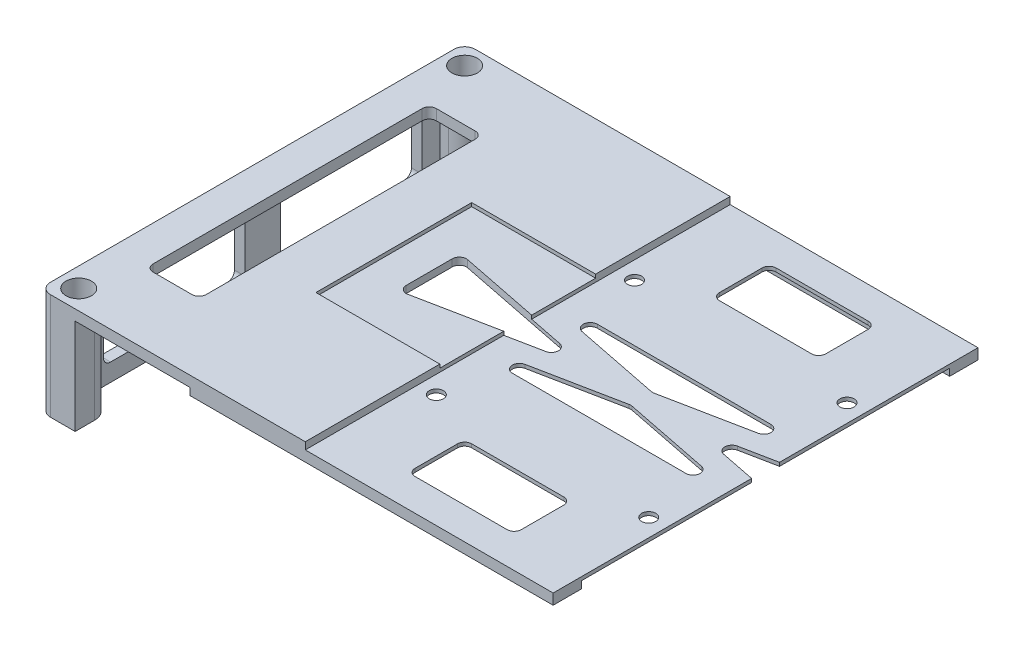
SolidWorks part; units mm, degrees
material "ABS"
ref_plane "前基準面" through (0, 0, 0) normal (0, 0, 1) x (1, 0, 0)
ref_plane "上基準面" through (0, 0, 0) normal (0, 1, 0) x (1, 0, 0)
ref_plane "右基準面" through (0, 0, 0) normal (1, 0, 0) x (0, 0, -1)
sketch "草圖8" plane through (0, 0, 0) normal (0, 1, 0) x (1, 0, 0)
  line L1 (-110, 60) -> (110, 60)
  line L2 (-110, 60) -> (-110, -60)
  line L3 (-110, -60) -> (110, -60)
  line L4 (110, 60) -> (110, -60)
extrude "填料-伸長6" add sketch "草圖8" along normal blind 3
sketch "草圖10" plane through (0, 0, 0) normal (0, -1, 0) x (1, 0, 0)
  line L1 (-110, 60) -> (-100, 60)
  line L2 (-110, 60) -> (-110, -60)
  line L3 (-110, -60) -> (-100, -60)
  line L4 (-100, 60) -> (-100, -60)
  line L5 (0, 0) -> (0, 67.9588) construction
  line L6 (0, 0) -> (59.8785, 0) construction
  line L7 (110, -60) -> (100, -60)
  line L8 (100, 60) -> (100, -60)
  line L9 (110, 60) -> (100, 60)
  line L10 (110, 60) -> (110, -60)
  dimension "D2" = 10
extrude "填料-伸長7" add sketch "草圖10" along normal blind 27
sketch "草圖9" plane through (0, 0, 0) normal (0, 1, 0) x (1, 0, 0)
  line L0 (-1000, 0) -> (49000, 0) construction
  line L1 (0, -994.7968) -> (0, 49005.2032) construction
  line L2 (110, 60) -> (-110, 60) construction
  line L4 (110, -60) -> (110, 60) construction
  circle A0 centre (104.5, 54.5) radius 2.05
  circle A1 centre (-104.5, 54.5) radius 2.05
  circle A2 centre (-104.5, -54.5) radius 2.05
  circle A3 centre (104.5, -54.5) radius 2.05
  circle A6 centre (30, 28) radius 2
  circle A7 centre (-30, 28) radius 2
  circle A8 centre (30, -28) radius 2
  circle A9 centre (-30, -28) radius 2
  dimension "D1" = 4.1
  dimension "D5" = 4
  dimension "D2" = 5.5
  dimension "D3" = 5.5
  dimension "D6" = 30
  dimension "D7" = 28
extrude "除料-伸長1" cut sketch "草圖9" against normal through all and the other way through all contours A1 | A2 | A0 | A3
sketch "草圖11" plane through (0, 3, 0) normal (0, 1, 0) x (1, 0, 0)
  line L0 (0.0013, 21.2615) -> (0.0013, 0) construction
  line L1 (0.0013, 0) -> (-26.9987, 0) construction
  line L2 (110, -60) -> (110, 60) construction
  line L3 (110, 60) -> (-110, 60) construction
  circle A0 centre (-104.4974, 54.5) radius 3.6
  circle A1 centre (-104.4974, -54.5) radius 3.6
  circle A2 centre (104.5, -54.5) radius 3.6
  circle A3 centre (104.5, 54.5) radius 3.6
  dimension "D1" = 7.2
  dimension "D2" = 5.5
  dimension "D4" = 5.5
extrude "除料-伸長2" cut sketch "草圖11" against normal blind 22 contours A1 | A0 | A3 | A2
sketch "草圖13" plane through (0, 0, 0) normal (1, 0, 0) x (0, 0, -1)
  line L0 (0, 0) -> (0, -20.0336) construction
  line L2 (-45, -3.5) -> (-5, -3.5)
  line L3 (-45, -3.5) -> (-45, -22)
  line L4 (-45, -22) -> (-5, -22)
  line L5 (-5, -3.5) -> (-5, -22)
  line L6 (60, -27) -> (-60, -27) construction
  line L8 (45, -3.5) -> (45, -22)
  line L9 (5, -3.5) -> (5, -22)
  line L10 (45, -22) -> (5, -22)
  line L11 (45, -3.5) -> (5, -3.5)
  line L12 (-60, 3) -> (-60, -27) construction
  dimension "D1" = 18.5
  dimension "D2" = 5
  dimension "D3" = 15
  dimension "D4" = 10
extrude "除料-伸長4" cut sketch "草圖13" against normal through all both and the other way through all
sketch "草圖14" plane through (0, 3, 0) normal (0, 1, 0) x (1, 0, 0)
  line L0 (0, 0) -> (-46.215, 0) construction
  line L1 (0, 0) -> (0, 32.6806) construction
  line L3 (-70, -22) -> (70, -22)
  line L4 (-70, -22) -> (-70, 22)
  line L5 (-70, 22) -> (70, 22)
  line L6 (70, -22) -> (70, 22)
  line L7 (-70, -22) -> (70, 22) construction
  line L8 (-70, 22) -> (70, -22) construction
  dimension "D1" = 140
  dimension "D2" = 44
extrude "除料-伸長7" cut sketch "草圖14" against normal blind 1
sketch "草圖15" plane through (0, 3, 0) normal (0, 1, 0) x (1, 0, 0)
  line L0 (0, 0) -> (27.6246, 0) construction
  line L1 (-100, 40) -> (-85, 40)
  line L2 (-100, 40) -> (-100, -40)
  line L3 (-100, -40) -> (-85, -40)
  line L4 (-85, 40) -> (-85, -40)
  line L5 (0, 0) -> (0, 35.214) construction
  line L6 (100, 5) -> (85, 5)
  line L7 (85, 45) -> (85, 5)
  line L8 (100, 45) -> (85, 45)
  line L9 (100, 45) -> (100, 5)
  line L10 (70, 22) -> (-70, 22) construction
  line L11 (-44.7029, -12) -> (44.7029, -12)
  line L12 (-60, -8.9406) -> (-60, 8.9406)
  line L13 (-44.7029, 12) -> (44.7029, 12)
  line L14 (60, -8.9406) -> (60, 8.9406)
  line L15 (-15, -35) -> (15, -35)
  line L16 (0, -3.0594) -> (44.7029, -12)
  line L17 (-70, 22) -> (-70, -22) construction
  line L18 (-60, 8.9406) -> (-15.2971, 0)
  line L19 (-44.7029, -12) -> (0, -3.0594)
  line L20 (-44.7029, 12) -> (0, 3.0594)
  line L21 (-60, -8.9406) -> (-15.2971, 0)
  line L22 (-15, 51) -> (15, 51)
  line L23 (-15, 51) -> (-15, 35)
  line L24 (-15, 35) -> (15, 35)
  line L25 (15, 51) -> (15, 35)
  line L26 (15, -51) -> (15, -35)
  line L27 (-15, -51) -> (15, -51)
  line L28 (15.2971, 0) -> (60, -8.9406)
  line L29 (0, 3.0594) -> (44.7029, 12)
  line L30 (15.2971, 0) -> (60, 8.9406)
  line L31 (-15, -51) -> (-15, -35)
  line L32 (100, -45) -> (100, -5)
  line L33 (100, -45) -> (85, -45)
  line L34 (85, -45) -> (85, -5)
  line L35 (100, -5) -> (85, -5)
  line L36 (110, 60) -> (-110, 60) construction
  dimension "D1" = 40
  dimension "D2" = 85
  dimension "D3" = 15
  dimension "D4" = 10
  dimension "D5" = 10
  dimension "D6" = 30
  dimension "D7" = 16
  dimension "D8" = 35
  dimension "D9" = 85
  dimension "D10" = 80
  dimension "D11" = 15
extrude "除料-伸長8" cut sketch "草圖15" against normal through all
extrude "除料-伸長9" cut sketch "草圖9<5>" along normal through all contours A7 | A6 | A9 | A8
sketch "草圖9<5>" plane through (0, 0, 0) normal (0, 1, 0) x (1, 0, 0) same geometry as "草圖9"
sketch "草圖19" plane through (0, -27, 0) normal (0, -1, 0) x (1, 0, 0)
  line L5 (0, -57.1205) -> (0, 57.1205) construction
  line L6 (0, 0) -> (-76.5655, 0) construction
  line L12 (-100, 54.5) -> (-100, -54.5)
  line L15 (-110, 60) -> (-110, -60) construction
  line L16 (-104.5, 50) -> (-107, 50)
  line L18 (-104.5, -50) -> (-107, -50)
  line L19 (-107, 50) -> (-107, -50)
  line L20 (100, 54.5) -> (100, -54.5)
  line L21 (104.5, -50) -> (107, -50)
  line L22 (107, 50) -> (107, -50)
  line L23 (104.5, 50) -> (107, 50)
  arc A0 (-104.5, 50) -> (-100, 54.5) centre (-104.5, 54.5) ccw
  arc A1 (-104.5, -50) -> (-100, -54.5) centre (-104.5, -54.5) cw
  arc A4 (104.5, 50) -> (100, 54.5) centre (104.5, 54.5) cw
  arc A5 (104.5, -50) -> (100, -54.5) centre (104.5, -54.5) ccw
  point P10 (0, 0)
  dimension "D2" = 9
  dimension "D1" = 3
extrude "除料-伸長13" cut sketch "草圖19" against normal blind 27
sketch "草圖20" plane through (0, 0, 0) normal (0, -1, 0) x (1, 0, 0)
  line L0 (0, 0) -> (0, 103.9697) construction
  line L1 (0, 0) -> (143.2508, 0) construction
  line L2 (-100, 60) -> (100, 60) construction
  line L3 (-67.5, 60) -> (67.5, 60)
  line L4 (-67.5, 60) -> (-67.5, 52)
  line L5 (-67.5, 52) -> (67.5, 52)
  line L6 (67.5, 60) -> (67.5, 52)
  line L7 (-67.5, -52) -> (67.5, -52)
  line L8 (67.5, -60) -> (67.5, -52)
  line L9 (-67.5, -60) -> (67.5, -60)
  line L10 (-67.5, -60) -> (-67.5, -52)
  line L12 (-59, 32.5) -> (-39, 32.5)
  line L13 (-59, 32.5) -> (-59, 25)
  line L14 (-59, 25) -> (-54, 25)
  line L15 (-39, 32.5) -> (-39, 29.5)
  line L28 (-85, 40) -> (-85, -40) construction
  line L31 (-54, 25) -> (-54, 29.5)
  line L32 (-54, 29.5) -> (-39, 29.5)
  line L33 (54, 29.5) -> (39, 29.5)
  line L34 (54, 25) -> (54, 29.5)
  line L35 (39, 32.5) -> (39, 29.5)
  line L36 (59, 25) -> (54, 25)
  line L37 (59, 32.5) -> (59, 25)
  line L38 (59, 32.5) -> (39, 32.5)
  line L39 (59, -32.5) -> (39, -32.5)
  line L40 (59, -32.5) -> (59, -25)
  line L41 (59, -25) -> (54, -25)
  line L42 (39, -32.5) -> (39, -29.5)
  line L43 (54, -25) -> (54, -29.5)
  line L44 (54, -29.5) -> (39, -29.5)
  line L45 (-54, -29.5) -> (-39, -29.5)
  line L46 (-54, -25) -> (-54, -29.5)
  line L47 (-39, -32.5) -> (-39, -29.5)
  line L48 (-59, -25) -> (-54, -25)
  line L49 (-59, -32.5) -> (-59, -25)
  line L50 (-59, -32.5) -> (-39, -32.5)
  dimension "D1" = 135
  dimension "D2" = 8
  dimension "D3" = 20
  dimension "D4" = 7.5
  dimension "D5" = 26
  dimension "D6" = 25
  dimension "D7" = 3
  dimension "D8" = 5
extrude "填料-伸長8" add sketch "草圖20" along normal blind 2
fillet "圓角1" radius 3 4 edges at (-110, -12, 60) (-110, -12, -60) (110, -12, -60) (110, -12, 60)
fillet "圓角2" radius 2 49 edges at (-107, 0, 0) (107, 0, 0) (108.5, -3.5, -5) (108.5, -3.5, 45) (108.5, -22, 45) (108.5, -22, -5) (108.5, -3.5, -45) (108.5, -3.5, 5) (108.5, -22, 5) (108.5, -22, -45) (-108.5, -22, -45) (-108.5, -22, 5) (-108.5, -3.5, -45) (-108.5, -3.5, 5) (-108.5, -22, 45) (-108.5, -3.5, 45) (-108.5, -3.5, -5) (-108.5, -22, -5) (60, 1, -8.9406) (44.7029, 1, -12) (-44.7029, 1, -12) (0, 1, 3.0594) (-44.7029, 1, 12) (44.7029, 1, 12) (-15.2971, 1, 0) (0, 1, -3.0594) (60, 1, 8.9406) (100, 1.5, -5) (15, 1.5, -35) (100, 1.5, 45) (15, 1.5, 51) (-85, 1.5, 40) (-15, 1.5, 51) (85, 1.5, -5) (15.2971, 1, 0) (-100, 1.5, 40) (-15, 1.5, -35) (-60, 1, 8.9406) (-60, 1, -8.9406) (15, 1.5, 35) (-15, 1.5, 35) (85, 1.5, 5) (85, 1.5, -45) (100, 1.5, 5) (100, 1.5, -45) (15, 1.5, -51) (-15, 1.5, -51) (-85, 1.5, -40) (-100, 1.5, -40)
sketch "草圖21" plane through (0, 0, 0) normal (0, 0, 1) x (1, 0, 0)
  line L0 (0, 0) -> (0, 39.2806) construction
  line L1 (110, 3) -> (-35, 3)
  line L2 (110, 3) -> (110, -27)
  line L3 (110, -27) -> (35, -27)
  line L4 (-35, 3) -> (-35, 1)
  line L7 (-35, 1) -> (35, 1)
  line L8 (35, -27) -> (35, 1)
  point P10 (110, -27)
  dimension "D1" = 2
  dimension "D2" = 70
  dimension "D3" = 35
extrude "除料-伸長14" cut sketch "草圖21" against normal through all both and the other way through all
